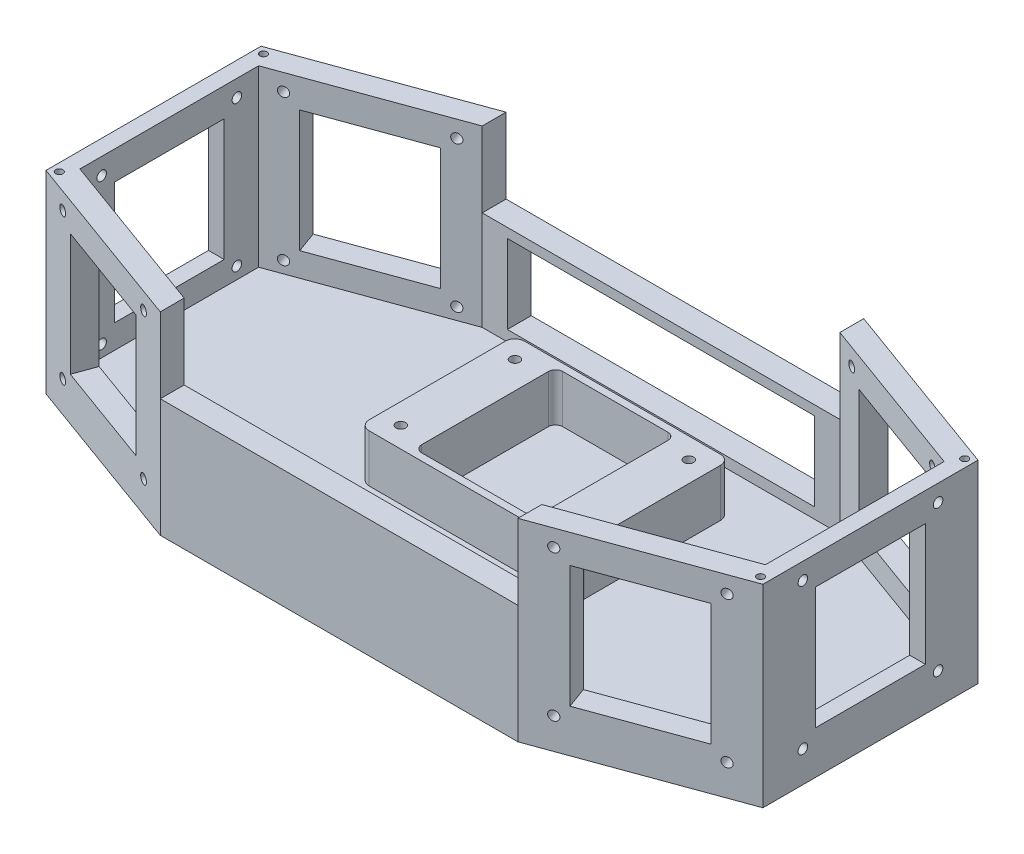
SolidWorks part; units mm, degrees
material "ABS"
ref_plane "Front Plane" through (0, 0, 0) normal (0, 0, 1) x (1, 0, 0)
ref_plane "Top Plane" through (0, 0, 0) normal (0, 1, 0) x (1, 0, 0)
ref_plane "Right Plane" through (0, 0, 0) normal (1, 0, 0) x (0, 0, -1)
sketch "Sketch1" plane through (0, 0, 0) normal (0, 1, 0) x (1, 0, 0)
  line L0 (-150, 0) -> (150, 0) construction
  line L1 (-150, 45) -> (-150, -45)
  line L2 (140.0883, -41.1583) -> (79.948, -63.0476) construction
  line L3 (-140.0883, 41.1583) -> (-142.4825, 47.7362) construction
  line L4 (-140.0883, 41.1583) -> (-79.948, 63.0476) construction
  line L5 (-150, 45) -> (-74.8246, 72.3616)
  line L6 (-79.948, 63.0476) -> (-82.3421, 69.6255) construction
  line L7 (-143, 32) -> (-143, -32) construction
  line L8 (-140.0883, -41.1583) -> (-142.4825, -47.7362) construction
  line L9 (-79.948, -63.0476) -> (-82.3421, -69.6255) construction
  line L10 (-140.0883, -41.1583) -> (-79.948, -63.0476) construction
  line L11 (-150, -45) -> (-74.8246, -72.3616)
  line L12 (0, 74.8501) -> (0, -82.9126) construction
  line L13 (79.948, -63.0476) -> (82.3421, -69.6255) construction
  line L14 (140.0883, -41.1583) -> (142.4825, -47.7362) construction
  line L15 (143, 32) -> (143, -32) construction
  line L16 (79.948, 63.0476) -> (82.3421, 69.6255) construction
  line L17 (140.0883, 41.1583) -> (79.948, 63.0476) construction
  line L18 (140.0883, 41.1583) -> (142.4825, 47.7362) construction
  line L19 (150, -45) -> (74.8246, -72.3616)
  line L20 (150, 45) -> (74.8246, 72.3616)
  line L21 (150, 45) -> (150, -45)
  line L22 (-74.8246, 72.3616) -> (74.8246, 72.3616)
  line L23 (-74.8246, -72.3616) -> (74.8246, -72.3616)
  point P0 (0, 0)
  point P3 (-150, 0)
  point P10 (-143, 0)
  point P13 (0, 0)
  point P37 (143, 0)
  dimension "D1" = 7
  dimension "D2" = 90
  dimension "D3" = 64
  dimension "D4" = 300
  dimension "D5" = 7
  dimension "D6" = 8
  dimension "D7" = 80
  dimension "D8" = 110
extrude "Boss-Extrude1" add sketch "Sketch1" along normal blind 8
sketch "Sketch2" plane through (0, 8, 0) normal (0, 1, 0) x (1, 0, 0)
  line L0 (0, 72.3616) -> (0, -72.3616) construction
  line L1 (74.8246, 72.3616) -> (-74.8246, 72.3616) construction
  line L2 (-74.8246, -72.3616) -> (74.8246, -72.3616) construction
  line L3 (-74.8246, -72.3616) -> (-74.8246, -62.3616) construction
  line L4 (-74.8246, -62.3616) -> (-64.3246, -62.3616) construction
  line L5 (-64.3246, -62.3616) -> (-64.3246, -72.3616) construction
  line L6 (-64.3246, -72.3616) -> (-74.8246, -72.3616) construction
  line L7 (64.3246, -72.3616) -> (74.8246, -72.3616) construction
  line L8 (64.3246, -62.3616) -> (64.3246, -72.3616) construction
  line L9 (74.8246, -62.3616) -> (64.3246, -62.3616) construction
  line L10 (74.8246, -72.3616) -> (74.8246, -62.3616) construction
  line L11 (-150, 0) -> (150, 0) construction
  line L12 (-150, 45) -> (-150, -45) construction
  line L13 (150, -45) -> (150, 45) construction
  line L14 (74.8246, 72.3616) -> (74.8246, 62.3616)
  line L15 (74.8246, 62.3616) -> (64.3246, 62.3616)
  line L16 (64.3246, 62.3616) -> (64.3246, 72.3616)
  line L17 (64.3246, 72.3616) -> (74.8246, 72.3616)
  line L18 (-64.3246, 72.3616) -> (-74.8246, 72.3616)
  line L19 (-64.3246, 62.3616) -> (-64.3246, 72.3616)
  line L20 (-74.8246, 62.3616) -> (-64.3246, 62.3616)
  line L21 (-74.8246, 72.3616) -> (-74.8246, 62.3616)
  dimension "D1" = 10.5
  dimension "D2" = 10
extrude "Boss-Extrude2" add sketch "Sketch2" along normal blind 37.5
sketch "Sketch4" plane through (0, 8, 0) normal (0, 1, 0) x (1, 0, 0)
  line L1 (-64.3246, 72.3616) -> (64.3246, 72.3616)
  line L2 (-64.3246, 72.3616) -> (-64.3246, 62.3616)
  line L3 (-64.3246, 62.3616) -> (64.3246, 62.3616)
  line L4 (64.3246, 72.3616) -> (64.3246, 62.3616)
extrude "Boss-Extrude4" add sketch "Sketch4" along normal blind 4.5
sketch "Sketch5" plane through (0, 8, 0) normal (0, 1, 0) x (1, 0, 0)
  line L0 (-74.8246, 62.3616) -> (-87.0406, 57.9153)
  line L1 (-74.8246, 72.3616) -> (-150, 45) construction
  line L2 (-74.8246, 72.3616) -> (-74.8246, 62.3616)
  line L3 (-74.8246, 72.3616) -> (-150, 45)
  line L4 (-87.0406, 57.9153) -> (-140.6031, 38.4202)
  line L5 (-150, 45) -> (-140.6031, 38.4202) construction
  line L6 (-74.8246, -72.3616) -> (-74.8246, -62.3616)
  line L7 (-140.6031, 38.4202) -> (-143.4222, 37.3941)
  line L8 (-150, 45) -> (-143.4222, 37.3941) construction
  line L9 (-150, 0) -> (-74.8246, 0) construction
  line L10 (-150, 45) -> (-150, -45) construction
  line L11 (-79.6003, 0) -> (86.9407, 0) construction
  line L12 (-124.0599, 0) -> (-121.8599, 0) construction
  line L13 (-74.8246, -62.3616) -> (-87.0406, -57.9153)
  line L14 (-140.6031, -38.4202) -> (-143.4222, -37.3941)
  line L15 (-87.0406, -57.9153) -> (-140.6031, -38.4202)
  line L16 (-150, -45) -> (-143.4222, -37.3941) construction
  line L17 (-74.8246, -72.3616) -> (-150, -45)
  line L18 (-143.4222, 37.3941) -> (-143.4222, -37.3941)
  line L19 (-150, 45) -> (-150, -45)
  line L20 (0, 72.1209) -> (0, -72.3616) construction
  line L21 (-74.8246, -72.3616) -> (74.8246, -72.3616) construction
  line L22 (150, -45) -> (143.4222, -37.3941) construction
  line L23 (150, 0) -> (74.8246, 0) construction
  line L24 (150, 45) -> (143.4222, 37.3941) construction
  line L25 (150, 45) -> (140.6031, 38.4202) construction
  line L26 (150, 45) -> (150, -45)
  line L27 (143.4222, 37.3941) -> (143.4222, -37.3941)
  line L28 (74.8246, -72.3616) -> (150, -45)
  line L29 (87.0406, -57.9153) -> (140.6031, -38.4202)
  line L30 (140.6031, -38.4202) -> (143.4222, -37.3941)
  line L31 (74.8246, -62.3616) -> (87.0406, -57.9153)
  line L32 (140.6031, 38.4202) -> (143.4222, 37.3941)
  line L33 (74.8246, -72.3616) -> (74.8246, -62.3616)
  line L34 (87.0406, 57.9153) -> (140.6031, 38.4202)
  line L35 (74.8246, 72.3616) -> (150, 45)
  line L36 (74.8246, 72.3616) -> (74.8246, 62.3616)
  line L37 (74.8246, 62.3616) -> (87.0406, 57.9153)
  dimension "D1" = 13
  dimension "D2" = 55
  dimension "D3" = 3
extrude "Boss-Extrude5" add sketch "Sketch5" along normal blind 10
sketch "Sketch6" plane through (0, 45.5, 0) normal (0, 1, 0) x (1, 0, 0)
  line L1 (74.8246, 72.3616) -> (-74.8246, 72.3616)
  line L2 (74.8246, 72.3616) -> (74.8246, 62.3616)
  line L3 (74.8246, 62.3616) -> (-74.8246, 62.3616)
  line L4 (-74.8246, 72.3616) -> (-74.8246, 62.3616)
extrude "Boss-Extrude6" add sketch "Sketch6" along normal blind 4
sketch "Sketch7" plane through (32.0094, 0, -87.9451) normal (0.342, 0, -0.9397) x (-0.9397, 0, -0.342)
  line L0 (-85.563, 18) -> (-85.563, 0) construction
  line L1 (-125.563, 18) -> (-45.563, 18) construction
  line L2 (-125.563, 0) -> (-45.563, 0) construction
  line L3 (-113.853, 13) -> (-85.563, 13) construction
  circle A0 centre (-113.853, 13) radius 2
  circle A1 centre (-57.273, 13) radius 2
  dimension "D1" = 56.58
  dimension "D2" = 4
  dimension "D3" = 5
extrude "Cut-Extrude1" cut sketch "Sketch7" against normal up to next
ref_plane "Plane1" through (0, 0, 0) normal (1, 0, 0) x (0, 0, -1)
mirror "Mirror1" about plane through (0, 0, 0) normal (1, 0, 0) of "Cut-Extrude1"
ref_plane "Plane2" through (0, 0, 0) normal (0, 0, -1) x (-1, 0, 0)
mirror "Mirror2" about plane through (0, 0, 0) normal (0, 0, -1) of "Cut-Extrude1", "Mirror1"
sketch "Sketch8" plane through (150, 0, 0) normal (1, 0, 0) x (0, 0, -1)
  line L0 (0, 18) -> (0, 0) construction
  line L1 (-45, 18) -> (45, 18) construction
  line L2 (-28.29, 13) -> (28.29, 13) construction
  line L3 (0, -27.225) -> (0, 27.225) construction
  circle A0 centre (-28.29, 13) radius 2
  circle A1 centre (28.29, 13) radius 2
  point P8 (0, 13)
  dimension "D1" = 56.58
  dimension "D3" = 4
  dimension "D2" = 5
extrude "Cut-Extrude2" cut sketch "Sketch8" against normal up to next
mirror "Mirror3" about plane through (0, 0, 0) normal (1, 0, 0) of "Cut-Extrude2"
sketch "Sketch9" plane through (0, 18, 0) normal (0, 1, 0) x (1, 0, 0)
  line L0 (143.4222, 23) -> (150, 23)
  line L1 (143.4222, 37.3941) -> (143.4222, -37.3941) construction
  line L2 (150, -45) -> (150, 45) construction
  line L3 (150, 23) -> (150, 45)
  line L4 (150, 45) -> (134.0252, 50.8143)
  line L5 (150, 45) -> (74.8246, 72.3616) construction
  line L6 (134.0252, 50.8143) -> (130.8113, 41.9841)
  line L7 (74.8246, 62.3616) -> (143.4222, 37.3941) construction
  line L8 (130.8113, 41.9841) -> (143.4222, 37.3941)
  line L9 (143.4222, 37.3941) -> (143.4222, 23)
  line L12 (74.8246, 72.3616) -> (90.7994, 66.5473)
  line L13 (90.7994, 66.5473) -> (87.5854, 57.717)
  line L14 (87.5854, 57.717) -> (74.8246, 62.3616)
  line L15 (74.8246, 72.3616) -> (74.8246, 62.3616) construction
  line L16 (74.8246, 62.3616) -> (74.8246, 72.3616)
  line L17 (0, -70.7131) -> (0, 92.4677) construction
  line L18 (-74.8246, 62.3616) -> (-74.8246, 72.3616)
  line L19 (-87.5854, 57.717) -> (-74.8246, 62.3616)
  line L20 (-90.7994, 66.5473) -> (-87.5854, 57.717)
  line L21 (-74.8246, 72.3616) -> (-90.7994, 66.5473)
  line L22 (-143.4222, 37.3941) -> (-143.4222, 23)
  line L23 (-130.8113, 41.9841) -> (-143.4222, 37.3941)
  line L24 (-134.0252, 50.8143) -> (-130.8113, 41.9841)
  line L25 (-150, 45) -> (-134.0252, 50.8143)
  line L26 (-150, 23) -> (-150, 45)
  line L27 (-143.4222, 23) -> (-150, 23)
  line L28 (150, 0) -> (-150, 0) construction
  line L29 (-150, 45) -> (-150, -45) construction
  line L30 (143.4222, -37.3941) -> (143.4222, -23)
  line L31 (130.8113, -41.9841) -> (143.4222, -37.3941)
  line L32 (134.0252, -50.8143) -> (130.8113, -41.9841)
  line L33 (150, -45) -> (134.0252, -50.8143)
  line L34 (150, -23) -> (150, -45)
  line L35 (143.4222, -23) -> (150, -23)
  line L36 (-143.4222, -23) -> (-150, -23)
  line L37 (-150, -23) -> (-150, -45)
  line L38 (-150, -45) -> (-134.0252, -50.8143)
  line L39 (-134.0252, -50.8143) -> (-130.8113, -41.9841)
  line L40 (-130.8113, -41.9841) -> (-143.4222, -37.3941)
  line L41 (-143.4222, -37.3941) -> (-143.4222, -23)
  line L42 (-74.8246, -72.3616) -> (-90.7994, -66.5473)
  line L43 (-90.7994, -66.5473) -> (-87.5854, -57.717)
  line L44 (-87.5854, -57.717) -> (-74.8246, -62.3616)
  line L45 (-74.8246, -62.3616) -> (-74.8246, -72.3616)
  line L46 (74.8246, -62.3616) -> (74.8246, -72.3616)
  line L47 (87.5854, -57.717) -> (74.8246, -62.3616)
  line L48 (90.7994, -66.5473) -> (87.5854, -57.717)
  line L49 (74.8246, -72.3616) -> (90.7994, -66.5473)
  dimension "D1" = 22
  dimension "D2" = 17
  dimension "D3" = 17
extrude "Boss-Extrude8" add sketch "Sketch9" along normal blind 63
sketch "Sketch10" plane through (32.0094, 0, -87.9451) normal (0.342, 0, -0.9397) x (-0.9397, 0, -0.342)
  line L0 (-85.563, 0) -> (-85.563, 86.9159) construction
  line L1 (-125.563, 0) -> (-45.563, 0) construction
  line L2 (-113.853, 13) -> (-113.853, 74) construction
  circle A0 centre (-113.853, 74) radius 2
  circle A1 centre (-113.853, 13) radius 2 construction
  circle A2 centre (-57.273, 74) radius 2
  dimension "D1" = 61
extrude "Cut-Extrude3" cut sketch "Sketch10" against normal up to next
mirror "Mirror4" about plane through (0, 0, 0) normal (1, 0, 0) of "Cut-Extrude3"
mirror "Mirror5" about plane through (0, 0, 0) normal (0, 0, -1) of "Cut-Extrude3", "Mirror4"
sketch "Sketch11" plane through (150, 0, 0) normal (1, 0, 0) x (0, 0, -1)
  line L0 (-28.29, 13) -> (-28.29, 74) construction
  line L1 (0, 18) -> (0, 79.1024) construction
  line L2 (-23, 18) -> (23, 18) construction
  circle A0 centre (-28.29, 74) radius 2
  circle A1 centre (-28.29, 13) radius 2 construction
  circle A2 centre (28.29, 74) radius 2
  dimension "D1" = 61
extrude "Cut-Extrude4" cut sketch "Sketch11" against normal up to next
mirror "Mirror6" about plane through (0, 0, 0) normal (1, 0, 0) of "Cut-Extrude4"
sketch "Sketch12" plane through (0, 81, 0) normal (0, 1, 0) x (1, 0, 0)
  line L0 (130.8113, 41.9841) -> (87.5854, 57.717)
  line L1 (87.5854, 57.717) -> (90.7994, 66.5473)
  line L2 (90.7994, 66.5473) -> (134.0252, 50.8143)
  line L3 (134.0252, 50.8143) -> (130.8113, 41.9841)
  line L4 (0, 103.9036) -> (0, -116.4859) construction
  line L5 (143.4222, 23) -> (150, 23)
  line L6 (143.4222, 23) -> (143.4222, -23)
  line L7 (143.4222, -23) -> (150, -23)
  line L8 (150, 23) -> (150, -23)
  line L9 (150, 0) -> (-150, 0) construction
  line L10 (-150, 23) -> (-150, -23) construction
  line L11 (134.0252, -50.8143) -> (130.8113, -41.9841)
  line L12 (90.7994, -66.5473) -> (134.0252, -50.8143)
  line L13 (87.5854, -57.717) -> (90.7994, -66.5473)
  line L14 (130.8113, -41.9841) -> (87.5854, -57.717)
  line L15 (-130.8113, -41.9841) -> (-87.5854, -57.717)
  line L16 (-87.5854, -57.717) -> (-90.7994, -66.5473)
  line L17 (-90.7994, -66.5473) -> (-134.0252, -50.8143)
  line L18 (-134.0252, -50.8143) -> (-130.8113, -41.9841)
  line L19 (-150, 23) -> (-150, -23)
  line L20 (-143.4222, -23) -> (-150, -23)
  line L21 (-143.4222, 23) -> (-143.4222, -23)
  line L22 (-143.4222, 23) -> (-150, 23)
  line L23 (-134.0252, 50.8143) -> (-130.8113, 41.9841)
  line L24 (-90.7994, 66.5473) -> (-134.0252, 50.8143)
  line L25 (-87.5854, 57.717) -> (-90.7994, 66.5473)
  line L26 (-130.8113, 41.9841) -> (-87.5854, 57.717)
extrude "Boss-Extrude9" add sketch "Sketch12" against normal blind 12
sketch "Sketch13" plane through (0, 8, 0) normal (0, 1, 0) x (1, 0, 0)
  line L0 (0, 62.3616) -> (0, -72.3616) construction
  line L1 (-41, 46.2316) -> (-29, 46.2316)
  line L2 (-45, 42.2316) -> (-45, -14.7684)
  line L3 (-41, -18.7684) -> (-29, -18.7684)
  line L4 (45, 42.2316) -> (45, -14.7684)
  line L5 (-74.8246, 62.3616) -> (74.8246, 62.3616) construction
  line L6 (-74.8246, -72.3616) -> (74.8246, -72.3616) construction
  line L7 (-25, 40.2316) -> (-25, -12.7684)
  line L8 (25, 40.2316) -> (25, -12.7684)
  line L9 (29, 46.2316) -> (41, 46.2316)
  line L10 (29, -18.7684) -> (41, -18.7684)
  line L11 (-25, 46.2316) -> (25, 46.2316) construction
  line L12 (-25, -18.7684) -> (25, -18.7684) construction
  line L13 (-29, 46.2316) -> (29, 46.2316)
  line L14 (-22, 43.2316) -> (22, 43.2316)
  line L15 (-22, -15.7684) -> (22, -15.7684)
  line L16 (-29, -18.7684) -> (29, -18.7684)
  arc A0 (-45, -14.7684) -> (-41, -18.7684) centre (-41, -14.7684) ccw
  arc A1 (41, -18.7684) -> (45, -14.7684) centre (41, -14.7684) ccw
  arc A2 (41, 46.2316) -> (45, 42.2316) centre (41, 42.2316) cw
  arc A3 (-41, 46.2316) -> (-45, 42.2316) centre (-41, 42.2316) ccw
  arc A4 (-25, -12.7684) -> (-22, -15.7684) centre (-22, -12.7684) ccw
  arc A5 (25, -12.7684) -> (22, -15.7684) centre (22, -12.7684) cw
  arc A6 (25, 40.2316) -> (22, 43.2316) centre (22, 40.2316) ccw
  arc A7 (-25, 40.2316) -> (-22, 43.2316) centre (-22, 40.2316) cw
  point P10 (0, 46.2316)
  point P15 (45, -18.7684)
  point P18 (45, 46.2316)
  point P21 (-45, 46.2316)
  dimension "D4" = 4
  dimension "D7" = 3
  dimension "D9" = 3
  dimension "D1" = 65
  dimension "D2" = 90
  dimension "D3" = 16.13
  dimension "D5" = 20
  dimension "D6" = 25
  dimension "D8" = 3
extrude "Boss-Extrude10" add sketch "Sketch13" along normal blind 20
sketch "Sketch14" plane through (0, 28, 0) normal (0, 1, 0) x (1, 0, 0)
  line L0 (-45, 42.2316) -> (-45, -14.7684) construction
  line L1 (-36.37, 37.6066) -> (-36.37, -10.1434) construction
  line L2 (-45, 13.7316) -> (-25, 13.7316) construction
  line L3 (-25, -12.7684) -> (-25, 40.2316) construction
  circle A0 centre (-36.37, 37.6066) radius 2
  circle A1 centre (-36.37, -10.1434) radius 2
  point P10 (-36.37, 13.7316)
  dimension "D1" = 4
  dimension "D2" = 47.75
  dimension "D3" = 8.63
extrude "Cut-Extrude5" cut sketch "Sketch14" against normal blind 10
mirror "Mirror7" about plane through (0, 0, 0) normal (1, 0, 0) of "Cut-Extrude5"
sketch "Sketch15" plane through (0, 8, 0) normal (0, 1, 0) x (1, 0, 0)
  line L1 (-74.8246, -72.3616) -> (74.8246, -72.3616)
  line L2 (-74.8246, -72.3616) -> (-74.8246, -62.3616)
  line L3 (-74.8246, -62.3616) -> (74.8246, -62.3616)
  line L4 (74.8246, -72.3616) -> (74.8246, -62.3616)
extrude "Boss-Extrude11" add sketch "Sketch15" along normal blind 41.5
sketch "Sketch16" plane through (0, 0, -72.3616) normal (0, 0, -1) x (-1, 0, 0)
  line L0 (-74.8246, 81) -> (-47.5, 81)
  line L1 (0, 0) -> (0, 104.0722) construction
  line L2 (0, 44.55) -> (0, -44.55) construction
  line L3 (74.8246, 81) -> (47.5, 81)
  line L4 (-74.8246, 49.5) -> (74.8246, 49.5) construction
  line L5 (-74.8246, 81) -> (-74.8246, 49.5)
  line L6 (-74.8246, 49.5) -> (74.8246, 49.5)
  line L7 (74.8246, 49.5) -> (74.8246, 81)
  arc A0 (-47.5, 81) -> (47.5, 81) centre (0, 101.0635) ccw
  dimension "D1" = 95
sketch "Sketch17" plane through (0, 81, 0) normal (0, 1, 0) x (1, 0, 0)
  line L0 (150, -45) -> (123.1193, -26.178) construction
  line L1 (150, 0) -> (-150, 0) construction
  line L2 (150, -45) -> (150, 45) construction
  line L3 (-150, 45) -> (-150, -45) construction
  line L4 (0, 76.5626) -> (0, -108.8084) construction
  circle A0 centre (146.7234, -42.7057) radius 1.5
  circle A1 centre (146.7234, 42.7057) radius 1.5
  circle A2 centre (-146.7234, 42.7057) radius 1.5
  circle A3 centre (-146.7234, -42.7057) radius 1.5
  dimension "D2" = 3
  dimension "D1" = 55
  dimension "D3" = 4
extrude "Cut-Extrude6" cut sketch "Sketch17" against normal blind 10
